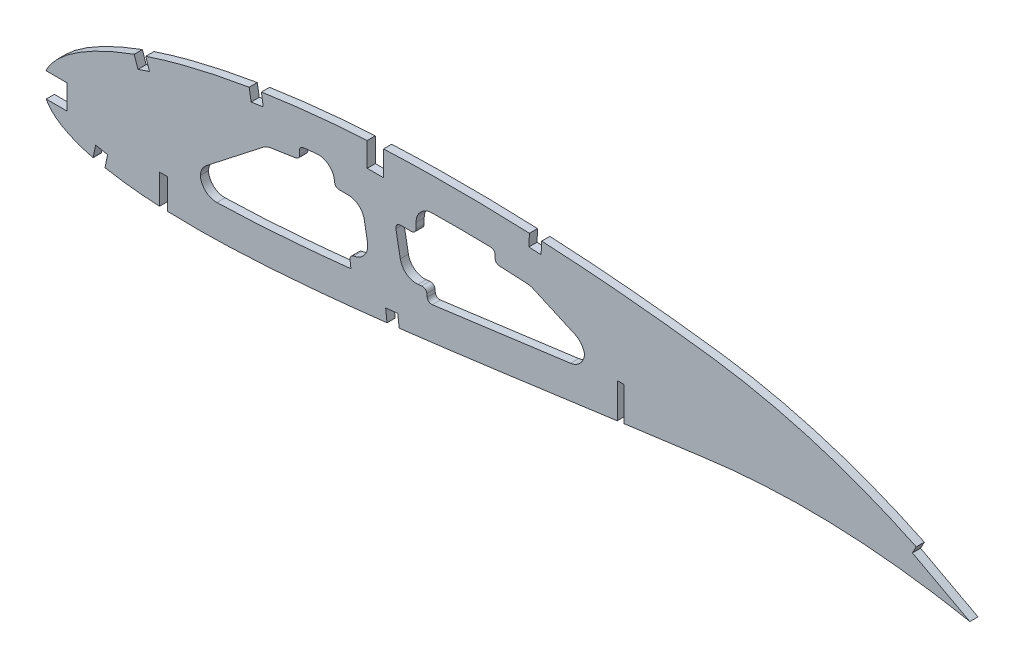
SolidWorks part; units mm, degrees
material "Plywood"
ref_plane "Front Plane" through (0, 0, 0) normal (0, 0, 1) x (1, 0, 0)
ref_plane "Top Plane" through (0, 0, 0) normal (0, 1, 0) x (1, 0, 0)
ref_plane "Right Plane" through (0, 0, 0) normal (1, 0, 0) x (0, 0, -1)
curve "Curve1"
  spline degree 3 poles (383.949, 0.5986, 0) (383.9196, 0.6168, 0) (383.802, 0.6894, 0) (383.5372, 0.8518, 0) (383.0962, 1.1224, 0) (382.4788, 1.4992, 0) (381.6856, 1.9812, 0) (380.716, 2.5651, 0) (379.5708, 3.249, 0) (378.2502, 4.0295, 0) (376.7543, 4.9032, 0) (375.0838, 5.8664, 0) (373.2387, 6.9137, 0) (371.2197, 8.0407, 0) (369.0276, 9.2423, 0) (366.6628, 10.5128, 0) (364.1261, 11.8459, 0) (361.4185, 13.2358, 0) (358.5405, 14.6749, 0) (355.4934, 16.1571, 0) (352.2782, 17.675, 0) (348.8962, 19.2207, 0) (345.3491, 20.7877, 0) (341.638, 22.3663, 0) (337.765, 23.9497, 0) (333.7318, 25.5289, 0) (329.5407, 27.0966, 0) (325.1933, 28.6428, 0) (320.6929, 30.1607, 0) (316.0417, 31.6403, 0) (311.2431, 33.0737, 0) (306.2997, 34.4516, 0) (301.2157, 35.767, 0) (295.9944, 37.0101, 0) (290.6401, 38.1728, 0) (285.1572, 39.2479, 0) (279.5502, 40.2249, 0) (273.8346, 41.1028, 0) (268.1025, 41.8331, 0) (262.3821, 42.5494, 0) (256.6703, 43.2222, 0) (250.8886, 43.8666, 0) (245.0428, 44.4788, 0) (239.1384, 45.057, 0) (233.1816, 45.5987, 0) (227.1785, 46.1022, 0) (221.135, 46.5647, 0) (215.0573, 46.9856, 0) (208.9515, 47.361, 0) (202.8242, 47.6908, 0) (196.6815, 47.9725, 0) (190.5298, 48.2044, 0) (184.3757, 48.385, 0) (178.2255, 48.5125, 0) (172.0859, 48.5861, 0) (165.9633, 48.6039, 0) (159.8643, 48.5655, 0) (153.7954, 48.4696, 0) (147.7632, 48.3149, 0) (141.7741, 48.1011, 0) (135.8345, 47.8283, 0) (129.951, 47.4942, 0) (124.1299, 47.1009, 0) (118.3778, 46.6469, 0) (112.701, 46.1319, 0) (107.1053, 45.5581, 0) (101.5971, 44.9239, 0) (96.1822, 44.2312, 0) (90.8666, 43.4813, 0) (85.6562, 42.6738, 0) (80.5566, 41.8111, 0) (75.5733, 40.894, 0) (70.7116, 39.9252, 0) (65.9768, 38.9049, 0) (61.3739, 37.8363, 0) (56.9076, 36.7211, 0) (52.5828, 35.5615, 0) (48.4038, 34.3602, 0) (44.375, 33.1199, 0) (40.5009, 31.842, 0) (36.7845, 30.5314, 0) (33.2304, 29.1889, 0) (29.8413, 27.8188, 0) (26.6212, 26.4228, 0) (23.5724, 25.0052, 0) (20.6984, 23.5677, 0) (18.0014, 22.1143, 0) (15.4839, 20.6472, 0) (13.1483, 19.1691, 0) (10.9958, 17.6837, 0) (9.0293, 16.1921, 0) (7.2493, 14.698, 0) (5.6571, 13.2036, 0) (4.255, 11.71, 0) (3.0428, 10.2198, 0) (2.0222, 8.7343, 0) (1.1933, 7.2547, 0) (0.558, 5.7822, 0) (0.1157, 4.3176, 0) (-0.1263, 2.863, 0) (-0.1866, 1.4174, 0) (-0.0621, 0.4718, 0) (0, 0, 0) knots 0 0 0 0 0.000254 0.001015 0.002283 0.004057 0.006331 0.009105 0.012374 0.016134 0.02038 0.025106 0.030306 0.035972 0.0421 0.048678 0.055702 0.06316 0.071046 0.07935 0.088063 0.097176 0.106678 0.116562 0.126814 0.137428 0.148394 0.1597 0.171338 0.183298 0.19557 0.208144 0.221012 0.234162 0.247587 0.261277 0.275223 0.289414 0.303771 0.317689 0.331784 0.34604 0.360444 0.374983 0.38964 0.404403 0.419257 0.434187 0.449177 0.464215 0.479284 0.49437 0.509458 0.524532 0.539579 0.554583 0.56953 0.584403 0.599191 0.613877 0.628447 0.642889 0.657186 0.671326 0.685294 0.699078 0.712665 0.726043 0.739198 0.752118 0.764792 0.777208 0.789356 0.801224 0.812804 0.824083 0.835055 0.84571 0.856038 0.866034 0.875689 0.884998 0.893953 0.902553 0.910789 0.918661 0.926166 0.933303 0.940071 0.946475 0.952518 0.958205 0.963547 0.968557 0.97325 0.977651 0.981787 0.985694 0.989415 0.993001 0.996508 1 1 1 1
curve "Curve2"
  spline degree 3 poles (0, 0, 0) (0.0986, -0.4654, 0) (0.2962, -1.3985, 0) (0.8332, -2.7416, 0) (1.5434, -4.0328, 0) (2.4415, -5.2686, 0) (3.5218, -6.4485, 0) (4.7818, -7.574, 0) (6.2202, -8.6443, 0) (7.8352, -9.659, 0) (9.6244, -10.6191, 0) (11.5859, -11.5241, 0) (13.7178, -12.3737, 0) (16.0178, -13.1667, 0) (18.4831, -13.9043, 0) (21.1113, -14.5848, 0) (23.8995, -15.2091, 0) (26.845, -15.7756, 0) (29.9446, -16.2848, 0) (33.195, -16.7366, 0) (36.593, -17.1311, 0) (40.1351, -17.4676, 0) (43.8179, -17.7467, 0) (47.6377, -17.9687, 0) (51.5909, -18.1343, 0) (55.6735, -18.2428, 0) (59.8817, -18.2959, 0) (64.2115, -18.2945, 0) (68.6589, -18.238, 0) (73.2199, -18.1297, 0) (77.8902, -17.9689, 0) (82.6657, -17.7575, 0) (87.5419, -17.4976, 0) (92.5144, -17.1902, 0) (97.5791, -16.8365, 0) (102.7313, -16.4394, 0) (107.9665, -16, 0) (113.2801, -15.5207, 0) (118.6674, -15.0039, 0) (124.1237, -14.4514, 0) (129.6442, -13.8657, 0) (135.2241, -13.2487, 0) (140.8584, -12.6036, 0) (146.5422, -11.9317, 0) (152.2705, -11.2369, 0) (158.0381, -10.5203, 0) (163.84, -9.7848, 0) (169.6711, -9.0339, 0) (175.5259, -8.2674, 0) (181.3995, -7.4908, 0) (187.2862, -6.7036, 0) (193.1809, -5.9096, 0) (199.0781, -5.1115, 0) (204.9721, -4.3094, 0) (210.8578, -3.5066, 0) (216.7295, -2.7054, 0) (222.5817, -1.9059, 0) (228.409, -1.112, 0) (234.2055, -0.3236, 0) (239.9659, 0.4577, 0) (245.6847, 1.2295, 0) (251.3565, 1.9909, 0) (256.9754, 2.7413, 0) (262.5357, 3.4812, 0) (267.9487, 4.188, 0) (273.2002, 4.8993, 0) (278.3079, 5.4825, 0) (283.3519, 5.9802, 0) (288.3377, 6.3883, 0) (293.259, 6.7125, 0) (298.1104, 6.9553, 0) (302.886, 7.1201, 0) (307.5799, 7.2116, 0) (312.186, 7.2323, 0) (316.6983, 7.1886, 0) (321.1107, 7.0842, 0) (325.4171, 6.9238, 0) (329.6115, 6.7126, 0) (333.688, 6.4566, 0) (337.6405, 6.1594, 0) (341.4634, 5.828, 0) (345.1508, 5.4673, 0) (348.6971, 5.0813, 0) (352.0971, 4.6782, 0) (355.3453, 4.2606, 0) (358.4369, 3.8354, 0) (361.3669, 3.4069, 0) (364.1307, 2.9806, 0) (366.7239, 2.5605, 0) (369.1422, 2.1521, 0) (371.3821, 1.7594, 0) (373.4394, 1.3862, 0) (375.3115, 1.0371, 0) (376.9946, 0.7139, 0) (378.4864, 0.4219, 0) (379.7842, 0.1625, 0) (380.886, -0.0608, 0) (381.79, -0.247, 0) (382.4947, -0.3932, 0) (382.9989, -0.4995, 0) (383.3019, -0.5627, 0) (383.4365, -0.5914, 0) (383.4701, -0.5986, 0) knots 0 0 0 0 0.003638 0.007293 0.011028 0.014901 0.018963 0.023258 0.027821 0.032679 0.037853 0.043362 0.049215 0.055422 0.061989 0.068918 0.076211 0.083868 0.091887 0.100266 0.109 0.118085 0.127515 0.137285 0.147388 0.157816 0.168563 0.179619 0.190977 0.202627 0.21456 0.226767 0.239236 0.251959 0.264924 0.27812 0.291536 0.30516 0.318981 0.332985 0.347163 0.361499 0.375981 0.390597 0.405333 0.420175 0.43511 0.450124 0.465203 0.480333 0.495501 0.51069 0.525887 0.541078 0.556247 0.571382 0.586466 0.601485 0.616424 0.631269 0.646007 0.660621 0.675098 0.689423 0.703582 0.716908 0.730009 0.742952 0.755726 0.76832 0.780724 0.792927 0.804916 0.816679 0.828204 0.839475 0.850481 0.861208 0.871639 0.881763 0.891564 0.901027 0.910139 0.918884 0.927249 0.935221 0.942785 0.949928 0.956638 0.962904 0.968712 0.974054 0.978918 0.983297 0.98718 0.990561 0.993433 0.995791 0.99763 0.998946 0.999737 1 1 1 1
sketch "Sketch1" plane through (0, 0, 0) normal (0, 0, 1) x (1, 0, 0)
  line L23 (366.7792, -0.5725) -> (370.31, -1.3257)
  line L24 (367.2372, 0.5725) -> (370.31, -1.3257)
  spline S4 degree 3 poles (0, 0) (0.0943, -0.4452) (0.2833, -1.3376) (0.797, -2.6223) (1.4762, -3.8573) (2.3353, -5.0392) (3.3685, -6.1679) (4.5736, -7.2443) (5.9495, -8.2681) (7.4942, -9.2386) (9.2055, -10.1569) (11.0816, -11.0225) (13.1207, -11.8351) (15.3206, -12.5936) (17.6786, -13.2991) (20.1924, -13.95) (22.8593, -14.5471) (25.6766, -15.0889) (28.6412, -15.576) (31.7502, -16.0081) (35.0002, -16.3855) (38.3882, -16.7073) (41.9107, -16.9743) (45.5643, -17.1866) (49.3453, -17.345) (53.2503, -17.4488) (57.2753, -17.4996) (61.4167, -17.4982) (65.6704, -17.4442) (70.0329, -17.3406) (74.5, -17.1868) (79.0676, -16.9846) (83.7315, -16.736) (88.4877, -16.442) (93.3319, -16.1037) (98.2599, -15.7239) (103.2672, -15.3035) (108.3495, -14.8451) (113.5023, -14.3509) (118.7211, -13.8224) (124.0014, -13.2622) (129.3383, -12.672) (134.7274, -12.055) (140.1638, -11.4124) (145.6428, -10.7478) (151.1593, -10.0624) (156.7087, -9.3589) (162.286, -8.6407) (167.886, -7.9075) (173.5039, -7.1648) (179.1344, -6.4118) (184.7725, -5.6524) (190.4131, -4.889) (196.0505, -4.1218) (201.68, -3.354) (207.2962, -2.5877) (212.8937, -1.823) (218.4673, -1.0636) (224.0115, -0.3095) (229.5212, 0.4377) (234.9911, 1.176) (240.416, 1.9042) (245.7903, 2.622) (251.1086, 3.3297) (256.286, 4.0057) (261.3089, 4.6861) (266.1943, 5.2438) (271.0188, 5.7199) (275.7875, 6.1102) (280.4947, 6.4204) (285.1349, 6.6526) (289.7027, 6.8102) (294.1922, 6.8977) (298.5979, 6.9175) (302.9137, 6.8757) (307.134, 6.7759) (311.253, 6.6224) (315.2649, 6.4204) (319.164, 6.1755) (322.9444, 5.8913) (326.6009, 5.5743) (330.1278, 5.2293) (333.5197, 4.8601) (336.7717, 4.4746) (339.8786, 4.0752) (342.8356, 3.6685) (345.6381, 3.2586) (348.2816, 2.8509) (350.7619, 2.449) (353.075, 2.0585) (355.2173, 1.6829) (357.1852, 1.3259) (358.9757, 0.992) (360.5855, 0.6828) (362.0124, 0.4036) (363.2537, 0.1554) (364.3076, -0.0582) (365.1722, -0.2363) (365.8463, -0.3761) (366.3285, -0.4777) (366.6183, -0.5382) (366.7471, -0.5657) (366.7792, -0.5725) knots 0 0 0 0 0.003638 0.007293 0.011028 0.014901 0.018963 0.023258 0.027821 0.032679 0.037853 0.043362 0.049215 0.055422 0.061989 0.068918 0.076211 0.083868 0.091887 0.100266 0.109 0.118085 0.127515 0.137285 0.147388 0.157816 0.168563 0.179619 0.190977 0.202627 0.21456 0.226767 0.239236 0.251959 0.264924 0.27812 0.291536 0.30516 0.318981 0.332985 0.347163 0.361499 0.375981 0.390597 0.405333 0.420175 0.43511 0.450124 0.465203 0.480333 0.495501 0.51069 0.525887 0.541078 0.556247 0.571382 0.586466 0.601485 0.616424 0.631269 0.646007 0.660621 0.675098 0.689423 0.703582 0.716908 0.730009 0.742952 0.755726 0.76832 0.780724 0.792927 0.804916 0.816679 0.828204 0.839475 0.850481 0.861208 0.871639 0.881763 0.891564 0.901027 0.910139 0.918884 0.927249 0.935221 0.942785 0.949928 0.956638 0.962904 0.968712 0.974054 0.978918 0.983297 0.98718 0.990561 0.993433 0.995791 0.99763 0.998946 0.999737 1 1 1 1
  spline S5 degree 3 poles (367.2372, 0.5725) (367.2091, 0.5899) (367.0967, 0.6594) (366.8434, 0.8147) (366.4216, 1.0735) (365.8311, 1.4339) (365.0724, 1.895) (364.145, 2.4534) (363.0497, 3.1075) (361.7865, 3.8541) (360.3558, 4.6898) (358.7579, 5.6111) (356.9931, 6.6127) (355.062, 7.6908) (352.9654, 8.84) (350.7035, 10.0552) (348.2772, 11.3303) (345.6874, 12.6597) (342.9347, 14.0361) (340.0202, 15.4538) (336.945, 16.9057) (333.7102, 18.3841) (330.3175, 19.8829) (326.7679, 21.3928) (323.0635, 22.9073) (319.2058, 24.4177) (315.1971, 25.9172) (311.039, 27.3961) (306.7345, 28.8479) (302.2857, 30.2631) (297.6959, 31.6342) (292.9677, 32.9521) (288.105, 34.2102) (283.111, 35.3992) (277.9897, 36.5112) (272.7455, 37.5396) (267.3825, 38.474) (261.9157, 39.3138) (256.4331, 40.0123) (250.9617, 40.6974) (245.4985, 41.341) (239.9685, 41.9573) (234.3771, 42.5429) (228.7297, 43.0959) (223.0322, 43.6139) (217.2904, 44.0955) (211.5099, 44.5379) (205.6967, 44.9405) (199.8567, 45.2996) (193.9961, 45.615) (188.1207, 45.8845) (182.2368, 46.1063) (176.3505, 46.279) (170.468, 46.4009) (164.5957, 46.4714) (158.7396, 46.4884) (152.9061, 46.4516) (147.1013, 46.3599) (141.3317, 46.212) (135.6032, 46.0075) (129.9222, 45.7465) (124.2948, 45.427) (118.7271, 45.0508) (113.2253, 44.6165) (107.7956, 44.1239) (102.4435, 43.5751) (97.175, 42.9685) (91.9958, 42.306) (86.9116, 41.5888) (81.9279, 40.8164) (77.0503, 39.9912) (72.2839, 39.114) (67.6338, 38.1874) (63.1051, 37.2115) (58.7025, 36.1894) (54.4306, 35.1228) (50.2941, 34.0137) (46.297, 32.8646) (42.4435, 31.6784) (38.7381, 30.4561) (35.1834, 29.2025) (31.784, 27.9184) (28.5424, 26.6079) (25.4625, 25.2727) (22.5464, 23.9168) (19.7975, 22.5419) (17.2178, 21.1517) (14.8099, 19.7485) (12.5761, 18.3347) (10.5172, 16.914) (8.6363, 15.4873) (6.9338, 14.0582) (5.4109, 12.6289) (4.0698, 11.2003) (2.9103, 9.775) (1.9341, 8.3541) (1.1413, 6.9389) (0.5337, 5.5305) (0.1107, 4.1296) (-0.1208, 2.7384) (-0.1785, 1.3557) (-0.0594, 0.4512) (0, 0) knots 0 0 0 0 0.000254 0.001015 0.002283 0.004057 0.006331 0.009105 0.012374 0.016134 0.02038 0.025106 0.030306 0.035972 0.0421 0.048678 0.055702 0.06316 0.071046 0.07935 0.088063 0.097176 0.106678 0.116562 0.126814 0.137428 0.148394 0.1597 0.171338 0.183298 0.19557 0.208144 0.221012 0.234162 0.247587 0.261277 0.275223 0.289414 0.303771 0.317689 0.331784 0.34604 0.360444 0.374983 0.38964 0.404403 0.419257 0.434187 0.449177 0.464215 0.479284 0.49437 0.509458 0.524532 0.539579 0.554583 0.56953 0.584403 0.599191 0.613877 0.628447 0.642889 0.657186 0.671326 0.685294 0.699078 0.712665 0.726043 0.739198 0.752118 0.764792 0.777208 0.789356 0.801224 0.812804 0.824083 0.835055 0.84571 0.856038 0.866034 0.875689 0.884998 0.893953 0.902553 0.910789 0.918661 0.926166 0.933303 0.940071 0.946475 0.952518 0.958205 0.963547 0.968557 0.97325 0.977651 0.981787 0.985694 0.989415 0.993001 0.996508 1 1 1 1
extrude "Boss-Extrude1" add sketch "Sketch1" along normal blind 3.175
sketch "Sketch2" plane through (0, 0, 0) normal (0, 0, -1) x (-1, 0, 0)
  line L0 (-226.1759, 13.2245) -> (-223.6359, 13.2245)
  line L1 (-226.1759, 0.0342) -> (-226.1759, -1.6012)
  line L2 (-48.3759, -5.601) -> (-48.3759, -17.018)
  line L4 (-226.1759, -1.6012) -> (-223.6359, -0.7835)
  line L5 (-223.6359, -0.7835) -> (-223.6359, 0.0342)
  line L7 (-132.5134, 45.7369) -> (-132.5134, 36.144)
  line L8 (-132.5134, 36.144) -> (-126.1634, 36.144)
  line L9 (-132.5134, 45.7369) -> (-132.5134, 48.5008)
  line L10 (-226.1759, 13.2245) -> (-226.1759, 0.0342)
  line L12 (-132.5134, 48.5008) -> (-126.1634, 46.56)
  line L13 (-126.1634, 46.56) -> (-126.1634, 45.7369)
  line L14 (-45.2009, -5.601) -> (-45.2009, -17.018)
  line L16 (-48.3759, -5.601) -> (-45.2009, -5.601)
  line L17 (-48.3759, -17.018) -> (-48.3759, -19.7506)
  line L19 (-126.1634, 45.7369) -> (-126.1634, 36.144)
  line L20 (-48.3759, -19.7506) -> (-45.2009, -18.0441)
  line L21 (-45.2009, -18.0441) -> (-45.2009, -17.018)
  line L22 (-223.6359, 13.2245) -> (-223.6359, 0.0342)
extrude "Cut-Extrude1" cut sketch "Sketch2" against normal blind 7.62
sketch "Sketch3" plane through (0, 0, 3.175) normal (0, 0, 1) x (1, 0, 0)
  line L1 (-0.4139, 6.4879) -> (9.1111, 6.4879)
  line L2 (133.8957, -12.1377) -> (134.1695, -14.4701)
  line L3 (9.1111, -3.0371) -> (9.1111, 6.4879)
  line L4 (138.6396, -11.5807) -> (138.9134, -13.9131)
  line L5 (24.9672, -9.877) -> (20.307, -8.9078)
  line L6 (134.1695, -14.4701) -> (138.9134, -13.9131)
  line L7 (23.9692, -14.6694) -> (24.9672, -9.877)
  line L9 (41.3214, 26.3939) -> (39.8106, 30.9067)
  line L11 (85.6243, 36.6261) -> (84.9023, 41.3353)
  line L13 (138.0771, -6.8447) -> (133.3478, -7.4064)
  line L15 (138.6396, -11.5807) -> (138.0771, -6.8447)
  line L17 (193.9411, 40.8593) -> (194.1833, 45.6146)
  line L19 (-0.4139, -3.0371) -> (-0.4139, 6.4879)
  line L21 (-0.4139, -3.0371) -> (9.1111, -3.0371)
  line L23 (20.307, -8.9078) -> (19.3375, -13.5718)
  line L25 (80.1398, 40.5723) -> (80.9168, 35.9044)
  line L27 (80.9168, 35.9044) -> (85.6243, 36.6261)
  line L29 (133.3478, -7.4064) -> (133.8957, -12.1377)
  line L31 (189.3949, 45.8428) -> (189.1847, 41.0997)
  line L33 (189.1847, 41.0997) -> (193.9411, 40.8593)
  line L35 (35.312, 29.3422) -> (36.8054, 24.882)
  line L37 (36.8054, 24.882) -> (41.3214, 26.3939)
  line L39 (19.3375, -13.5718) -> (19.0177, -14.9208)
  line L40 (23.9692, -14.6694) -> (23.6495, -16.0185)
  line L41 (19.0177, -14.9208) -> (23.6495, -16.0185)
  arc A1 (194.1833, 45.6146) -> (189.3949, 45.8428) centre (155.1187, -723.9718) ccw
  spline S1 degree 3 poles (39.8106, 30.9067) (39.3989, 30.7692) (37.8946, 30.2613) (36.3966, 29.7352) (35.312, 29.3422) knots 0 0 0 0 0.273428 1 1 1 1
  spline S3 degree 3 poles (84.9023, 41.3353) (83.9797, 41.1935) (82.3915, 40.9435) (80.8049, 40.6833) (80.1398, 40.5723) knots 0 0 0 0 0.580571 1 1 1 1
extrude "Cut-Extrude2" cut sketch "Sketch3" against normal blind 7.62
sketch "Sketch4" plane through (0, 0, 3.175) normal (0, 0, 1) x (1, 0, 0)
  line L0 (124.0505, 23.444) -> (119.8134, 23.444)
  line L1 (61.0759, 3.8422) -> (61.0759, -4.7919)
  line L2 (119.8135, -0.9342) -> (119.2755, 3.7114)
  line L3 (119.2755, 3.7114) -> (127.5024, 4.6885)
  line L4 (140.1395, 6.1895) -> (149.1905, 7.2645)
  line L5 (210.9359, 18.8713) -> (189.752, 28.3548)
  line L6 (113.4634, 23.444) -> (113.4634, 31.88)
  line L7 (99.4216, 30.4365) -> (100.1022, 25.9974)
  line L8 (100.1022, 25.9974) -> (86.8727, 23.9691)
  line L9 (61.0759, 3.8422) -> (86.8727, 23.9691)
  line L10 (210.9359, 25.8286) -> (210.9359, 25.9245)
  line L12 (189.752, 28.3548) -> (175.9385, 29.0531)
  line L13 (124.0505, 23.444) -> (113.4634, 23.444)
  line L15 (127.5024, 4.6885) -> (124.0505, 23.444)
  line L16 (175.9385, 29.0531) -> (176.1387, 33.5719)
  line L17 (145.2134, 33.6045) -> (145.2134, 23.444)
  line L18 (145.2134, 23.444) -> (136.9638, 23.444)
  line L19 (125.5627, 4.4581) -> (127.5024, 4.6885)
  line L20 (149.1905, 7.2645) -> (149.749, 2.5622)
  line L21 (210.9359, 10.7271) -> (210.9359, 18.8713)
  line L23 (140.1395, 6.1895) -> (136.9638, 23.444)
  line L33 (46.7884, 0.749) -> (84.2728, 29.9947) construction
  line L34 (224.9059, 19.5745) -> (191.2608, 34.6367) construction
  line L35 (134.9727, -0.8188) -> (129.3384, 29.794) construction
  line L90 (15.4611, 12.6036) -> (15.4611, -1.4142) construction
  line L91 (15.4611, -1.4142) -> (32.4788, -4.9532) construction
  line L92 (32.4788, -4.9532) -> (31.5192, -9.5611) construction
  line L93 (38.8509, -10.3626) -> (38.8509, 0.749) construction
  line L94 (38.8509, 0.749) -> (54.7259, 0.749) construction
  line L95 (54.7259, 0.749) -> (54.7259, -11.1139) construction
  line L96 (126.857, -6.5565) -> (126.3117, -1.8475) construction
  line L97 (126.3117, -1.8475) -> (143.6338, 0.2099) construction
  line L98 (143.6338, 0.2099) -> (144.1962, -4.5249) construction
  line L99 (217.2859, 5.1839) -> (217.2859, 19.5745) construction
  line L100 (217.2859, 19.5745) -> (232.5259, 19.5745) construction
  line L101 (232.5259, 19.5745) -> (232.5259, 7.2506) construction
  line L102 (200.2001, 38.9114) -> (199.9599, 34.1969) construction
  line L103 (199.9599, 34.1969) -> (182.5616, 35.0764) construction
  line L104 (182.5616, 35.0764) -> (182.7677, 39.7263) construction
  line L105 (138.8634, 39.7674) -> (138.8634, 29.794) construction
  line L106 (138.8634, 29.794) -> (119.8134, 29.794) construction
  line L107 (119.8134, 29.794) -> (119.8134, 38.7525) construction
  line L108 (92.1584, 35.9089) -> (92.8632, 31.3117) construction
  line L109 (92.8632, 31.3117) -> (75.6823, 28.6777) construction
  line L110 (75.6823, 28.6777) -> (74.9393, 33.1419) construction
  line L111 (47.9131, 26.7069) -> (49.3588, 22.3884) construction
  line L112 (49.3588, 22.3884) -> (32.7999, 16.8445) construction
  line L113 (32.7999, 16.8445) -> (31.4358, 20.9189) construction
  spline S1 degree 3 poles (61.0759, -4.7919) (65.956, -4.7644) (75.6976, -4.4951) (90.3945, -3.6335) (105.0964, -2.4282) (114.9126, -1.4532) (119.8135, -0.9342) knots 0.088297 0.088297 0.088297 0.088297 0.294057 0.499818 0.705579 0.911339 0.911339 0.911339 0.911339
  spline S3 degree 3 poles (113.4634, 31.88) (112.2906, 31.7785) (109.9455, 31.5663) (106.4329, 31.2203) (102.9244, 30.8456) (100.5889, 30.5762) (99.4216, 30.4365) knots 0.248835 0.248835 0.248835 0.248835 0.377634 0.506434 0.635234 0.764034 0.764034 0.764034 0.764034
  spline S5 degree 3 poles (176.1387, 33.5719) (173.5606, 33.6369) (168.4029, 33.7373) (160.6696, 33.7956) (152.938, 33.7586) (147.7883, 33.6675) (145.2134, 33.6045) knots 0.147373 0.147373 0.147373 0.147373 0.325248 0.503123 0.680998 0.858873 0.858873 0.858873 0.858873
  spline S7 degree 3 poles (149.749, 2.5622) (154.8468, 3.2019) (165.0342, 4.5157) (180.3292, 6.5582) (195.6275, 8.6359) (205.8337, 10.0311) (210.9359, 10.7271) knots 0.086693 0.086693 0.086693 0.086693 0.296227 0.505762 0.715296 0.924831 0.924831 0.924831 0.924831
  spline S29 degree 3 poles (31.4358, 20.9189) (28.6531, 19.7653) (25.916, 18.5237) (21.9074, 16.4737) (20.5873, 15.759) (17.9891, 14.2488) (16.7091, 13.4524) (15.4611, 12.6036) knots 0 0 0 0 0.5 0.5 0.75 0.75 1 1 1 1 construction
  spline S30 degree 3 poles (31.5192, -9.5611) (33.9561, -9.8911) (36.4008, -10.1525) (38.8509, -10.3626) knots 0 0 0 0 1 1 1 1 construction
  spline S31 degree 3 poles (54.7259, -11.1139) (60.7538, -11.2031) (66.7785, -11.1065) (78.8236, -10.6715) (84.8424, -10.3327) (96.8659, -9.4865) (102.8724, -8.9793) (114.8725, -7.8476) (120.8667, -7.2227) (126.857, -6.5565) knots 0 0 0 0 0.25 0.25 0.5 0.5 0.75 0.75 1 1 1 1 construction
  spline S32 degree 3 poles (144.1962, -4.5249) (156.3939, -3.0317) (168.5773, -1.4251) (192.9351, 1.8535) (205.1095, 3.5262) (217.2859, 5.1839) knots 0 0 0 0 0.5 0.5 1 1 1 1 construction
  spline S33 degree 3 poles (232.5259, 7.2506) (236.7454, 7.8194) (240.9653, 8.3846) (247.2957, 9.2284) (249.406, 9.5085) (252.572, 9.9246) (253.6273, 10.0631) (255.7377, 10.3424) (256.7926, 10.4843) (258.903, 10.7638) (259.9585, 10.901) (262.0714, 11.1604) (263.1287, 11.2834) (266.3027, 11.6351) (268.4217, 11.8485) (274.7855, 12.4209) (279.0307, 12.7117) (287.5261, 13.1156) (291.7763, 13.2287) (300.2819, 13.2775) (304.5386, 13.2148) (317.3074, 12.7665) (325.7774, 12.1249) (334.2082, 11.1674) knots 0 0 0 0 0.125 0.125 0.1875 0.1875 0.21875 0.21875 0.25 0.25 0.28125 0.28125 0.3125 0.3125 0.375 0.375 0.5 0.5 0.625 0.625 0.75 0.75 1 1 1 1 construction
  spline S34 degree 3 poles (334.2082, 11.1674) (331.593, 12.3814) (328.9576, 13.5555) (323.6447, 15.8208) (320.9638, 16.9136) (312.8924, 20.0522) (307.47, 21.9608) (291.0773, 27.1309) (279.9822, 29.8393) (265.8998, 32.2791) (263.0735, 32.7235) (258.8151, 33.3063) (257.3929, 33.4883) (254.5475, 33.8483) (253.1245, 34.0271) (246.0062, 34.9053) (240.2966, 35.5479) (223.1381, 37.304) (211.6798, 38.2388) (200.2001, 38.9114) knots 0 0 0 0 0.0625 0.0625 0.125 0.125 0.25 0.25 0.5 0.5 0.5625 0.5625 0.59375 0.59375 0.625 0.625 0.75 0.75 1 1 1 1 construction
  spline S35 degree 3 poles (182.7677, 39.7263) (175.4529, 39.9792) (168.1344, 40.1179) (153.497, 40.1411) (146.178, 40.0263) (138.8634, 39.7674) knots 0 0 0 0 0.5 0.5 1 1 1 1 construction
  spline S36 degree 3 poles (119.8134, 38.7525) (110.5679, 38.0873) (101.3431, 37.1604) (92.1584, 35.9089) knots 0 0 0 0 1 1 1 1 construction
  spline S37 degree 3 poles (74.9393, 33.1419) (70.3845, 32.2908) (65.8479, 31.3424) (56.8317, 29.213) (52.3534, 28.033) (47.9131, 26.7069) knots 0 0 0 0 0.5 0.5 1 1 1 1 construction
extrude "Cut-Extrude3" cut sketch "Sketch4" against normal blind 7.62 contours L6 S3 L7 L8 L9 L1 S1 L2 L3 L15 L0 L13 | L20 S7 L21 L5 L12 L16 S5 L17 L18 L23 L4
fillet "Fillet1" radius 6.35 11 edges at (210.9359, 10.7271, 1.5875) (210.9359, 18.8713, 1.5875) (189.752, 28.3548, 1.5875) (140.1395, 6.1895, 1.5875) (145.2134, 33.6045, 1.5875) (113.4634, 31.88, 1.5875) (124.0505, 23.444, 1.5875) (127.5024, 4.6885, 1.5875) (86.8727, 23.9691, 1.5875) (61.0759, 3.8422, 1.5875) (61.0759, -4.7919, 1.5875)
fillet "Fillet2" radius 1.778 10 edges at (175.9385, 29.0531, 1.5875) (176.1387, 33.5719, 1.5875) (145.2134, 23.444, 1.5875) (136.9638, 23.444, 1.5875) (149.749, 2.5622, 1.5875) (149.1905, 7.2645, 1.5875) (119.2755, 3.7114, 1.5875) (113.4634, 23.444, 1.5875) (99.4216, 30.4365, 1.5875) (100.1022, 25.9974, 1.5875)
sketch "Sketch5" plane through (0, 0, 3.175) normal (0, 0, 1) x (1, 0, 0)
  line L0 (340.1843, 15.368) -> (338.6864, 12.5685)
  line L1 (340.1843, 15.368) -> (362.5799, 3.3848)
  line L2 (338.6864, 12.5685) -> (361.082, 0.5854)
  line L3 (362.5799, 3.3848) -> (361.082, 0.5854)
  line L33 (0.9572, 6.4879) -> (9.1111, 6.4879)
  line L34 (9.1111, 6.4879) -> (9.1111, -3.0371)
  line L35 (9.1111, -3.0371) -> (1.0356, -3.0371)
  line L36 (19.3035, -13.715) -> (19.3375, -13.5718)
  line L37 (19.3375, -13.5718) -> (20.307, -8.9078)
  line L38 (20.307, -8.9078) -> (24.9672, -9.877)
  line L39 (24.9672, -9.877) -> (23.9692, -14.6694)
  line L40 (23.9692, -14.6694) -> (23.9494, -14.7527)
  line L41 (45.2009, -17.1581) -> (45.2009, -5.601)
  line L42 (45.2009, -5.601) -> (48.3759, -5.601)
  line L43 (48.3759, -5.601) -> (48.3759, -17.3002)
  line L44 (133.8969, -12.1481) -> (133.8957, -12.1377)
  line L45 (133.8957, -12.1377) -> (133.3478, -7.4064)
  line L46 (133.3478, -7.4064) -> (138.0771, -6.8447)
  line L47 (138.0771, -6.8447) -> (138.6396, -11.5807)
  line L48 (138.6396, -11.5807) -> (138.6408, -11.5913)
  line L49 (223.6359, -0.3609) -> (223.6359, 13.2245)
  line L50 (223.6359, 13.2245) -> (226.1759, 13.2245)
  line L51 (226.1759, 13.2245) -> (226.1759, -0.0161)
  line L52 (366.7792, -0.5725) -> (370.31, -1.3257)
  line L53 (370.31, -1.3257) -> (367.2372, 0.5725)
  line L54 (194.1825, 45.5979) -> (193.9411, 40.8593)
  line L55 (193.9411, 40.8593) -> (189.1847, 41.0997)
  line L56 (189.1847, 41.0997) -> (189.394, 45.8221)
  line L57 (132.5134, 45.863) -> (132.5134, 36.144)
  line L58 (132.5134, 36.144) -> (126.1634, 36.144)
  line L59 (126.1634, 36.144) -> (126.1634, 45.5297)
  line L60 (84.9115, 41.2755) -> (85.6243, 36.6261)
  line L61 (85.6243, 36.6261) -> (80.9168, 35.9044)
  line L62 (80.9168, 35.9044) -> (80.1498, 40.512)
  line L63 (39.8414, 30.8149) -> (41.3214, 26.3939)
  line L64 (41.3214, 26.3939) -> (36.8054, 24.882)
  line L65 (36.8054, 24.882) -> (35.3441, 29.2465)
  line L66 (0.9572, 6.4879) -> (9.1111, 6.4879)
  line L67 (9.1111, 6.4879) -> (9.1111, -3.0371)
  line L68 (9.1111, -3.0371) -> (1.0356, -3.0371)
  line L69 (19.3035, -13.715) -> (19.3375, -13.5718)
  line L70 (19.3375, -13.5718) -> (20.307, -8.9078)
  line L71 (20.307, -8.9078) -> (24.9672, -9.877)
  line L72 (24.9672, -9.877) -> (23.9692, -14.6694)
  line L73 (23.9692, -14.6694) -> (23.9494, -14.7527)
  line L74 (45.2009, -17.1581) -> (45.2009, -5.601)
  line L75 (45.2009, -5.601) -> (48.3759, -5.601)
  line L76 (48.3759, -5.601) -> (48.3759, -17.3002)
  line L77 (133.8969, -12.1481) -> (133.8957, -12.1377)
  line L78 (133.8957, -12.1377) -> (133.3478, -7.4064)
  line L79 (133.3478, -7.4064) -> (138.0771, -6.8447)
  line L80 (138.0771, -6.8447) -> (138.6396, -11.5807)
  line L81 (138.6396, -11.5807) -> (138.6408, -11.5913)
  line L82 (223.6359, -0.3609) -> (223.6359, 13.2245)
  line L83 (223.6359, 13.2245) -> (226.1759, 13.2245)
  line L84 (226.1759, 13.2245) -> (226.1759, -0.0161)
  line L85 (366.7792, -0.5725) -> (370.31, -1.3257)
  line L86 (370.31, -1.3257) -> (367.2372, 0.5725)
  line L87 (194.1825, 45.5979) -> (193.9411, 40.8593)
  line L88 (193.9411, 40.8593) -> (189.1847, 41.0997)
  line L89 (189.1847, 41.0997) -> (189.394, 45.8221)
  line L90 (132.5134, 45.863) -> (132.5134, 36.144)
  line L91 (132.5134, 36.144) -> (126.1634, 36.144)
  line L92 (126.1634, 36.144) -> (126.1634, 45.5297)
  line L93 (84.9115, 41.2755) -> (85.6243, 36.6261)
  line L94 (85.6243, 36.6261) -> (80.9168, 35.9044)
  line L95 (80.9168, 35.9044) -> (80.1498, 40.512)
  line L96 (39.8414, 30.8149) -> (41.3214, 26.3939)
  line L97 (41.3214, 26.3939) -> (36.8054, 24.882)
  line L98 (36.8054, 24.882) -> (35.3441, 29.2465)
  spline S10 degree 3 poles (-1602.2186, 3650.0051) (487.3789, -131.6192) (206.9819, 94.095) (31.784, 27.9184) (28.5424, 26.6079) (25.4625, 25.2727) (22.5464, 23.9168) (19.7975, 22.5419) (17.2178, 21.1517) (14.8099, 19.7485) (12.5761, 18.3347) (10.5172, 16.914) (8.6363, 15.4873) (6.9338, 14.0582) (5.4109, 12.6289) (4.0698, 11.2003) (2.9103, 9.775) (1.9341, 8.3541) (-20.7317, -32.1056) (141.9822, -164.1766) (3983.6471, 308.8367) knots -0.544959 -0.544959 -0.544959 -0.544959 0.875689 0.884998 0.893953 0.902553 0.910789 0.918661 0.926166 0.933303 0.940071 0.946475 0.952518 0.958205 0.963547 0.968557 0.97325 0.977651 0.981787 1.329029 1.329029 1.329029 1.329029 only from (35.3441, 29.2465) to (0.9572, 6.4879)
  spline S11 degree 3 poles (2949.6013, -2676.1015) (249.915, 275.4573) (-28.9452, 37.9974) (2.3353, -5.0392) (3.3685, -6.1679) (4.5736, -7.2443) (5.9495, -8.2681) (7.4942, -9.2386) (9.2055, -10.1569) (11.0816, -11.0225) (13.1207, -11.8351) (15.3206, -12.5936) (116.8044, -42.9584) (283.113, 163.1405) (-1566.1338, -3678.5939) knots -0.405957 -0.405957 -0.405957 -0.405957 0.011028 0.014901 0.018963 0.023258 0.027821 0.032679 0.037853 0.043362 0.049215 0.055422 0.061989 0.897212 0.897212 0.897212 0.897212 only from (1.0356, -3.0371) to (19.3035, -13.715)
  spline S12 degree 3 poles (1065.9481, 3834.2944) (-164.825, 196.4215) (-84.1296, 2.9522) (28.6412, -15.576) (31.7502, -16.0081) (35.0002, -16.3855) (38.3882, -16.7073) (232.9912, -31.4577) (444.7882, 229.5505) (-286.8072, -3972.5643) knots -0.814737 -0.814737 -0.814737 -0.814737 0.083868 0.091887 0.100266 0.109 0.118085 0.127515 1.671641 1.671641 1.671641 1.671641 only from (23.9494, -14.7527) to (45.2009, -17.1581)
  spline S13 degree 3 poles (199.4193, 3945.0482) (-332.1325, 221.8434) (-143.9877, -12.2071) (53.2503, -17.4488) (57.2753, -17.4996) (61.4167, -17.4982) (65.6704, -17.4442) (70.0329, -17.3406) (74.5, -17.1868) (79.0676, -16.9846) (83.7315, -16.736) (88.4877, -16.442) (93.3319, -16.1037) (98.2599, -15.7239) (103.2672, -15.3035) (108.3495, -14.8451) (113.5023, -14.3509) (118.7211, -13.8224) (124.0014, -13.2622) (638.367, 43.6175) (1119.1061, 383.178) (1771.0517, -3371.2138) knots -1.411295 -1.411295 -1.411295 -1.411295 0.147388 0.157816 0.168563 0.179619 0.190977 0.202627 0.21456 0.226767 0.239236 0.251959 0.264924 0.27812 0.291536 0.30516 0.318981 0.332985 0.347163 0.361499 4.476796 4.476796 4.476796 4.476796 only from (48.3759, -17.3002) to (133.8969, -12.1481)
  spline S14 degree 3 poles (-1227.5928, 3651.2454) (-525.6727, 0.0992) (-185.4811, -50.9151) (145.6428, -10.7478) (151.1593, -10.0624) (156.7087, -9.3589) (162.286, -8.6407) (167.886, -7.9075) (173.5039, -7.1648) (179.1344, -6.4118) (184.7725, -5.6524) (190.4131, -4.889) (196.0505, -4.1218) (201.68, -3.354) (207.2962, -2.5877) (212.8937, -1.823) (746.9825, 70.9413) (1281.5459, 126.244) (2270.053, -3174.2029) knots -2.25069 -2.25069 -2.25069 -2.25069 0.390597 0.405333 0.420175 0.43511 0.450124 0.465203 0.480333 0.495501 0.51069 0.525887 0.541078 0.556247 0.571382 0.586466 0.601485 4.887536 4.887536 4.887536 4.887536 only from (138.6408, -11.5913) to (223.6359, -0.3609)
  spline S15 degree 3 poles (-1582.265, 3373.7911) (-655.3394, -155.2415) (-213.4868, -59.3515) (234.9911, 1.176) (240.416, 1.9042) (245.7903, 2.622) (251.1086, 3.3297) (256.286, 4.0057) (261.3089, 4.6861) (266.1943, 5.2438) (271.0188, 5.7199) (275.7875, 6.1102) (280.4947, 6.4204) (285.1349, 6.6526) (289.7027, 6.8102) (294.1922, 6.8977) (298.5979, 6.9175) (302.9137, 6.8757) (307.134, 6.7759) (311.253, 6.6224) (315.2649, 6.4204) (319.164, 6.1755) (322.9444, 5.8913) (326.6009, 5.5743) (330.1278, 5.2293) (333.5197, 4.8601) (336.7717, 4.4746) (339.8786, 4.0752) (342.8356, 3.6685) (345.6381, 3.2586) (348.2816, 2.8509) (350.7619, 2.449) (353.075, 2.0585) (355.2173, 1.6829) (357.1852, 1.3259) (358.9757, 0.992) (360.5855, 0.6828) (362.0124, 0.4036) (363.2537, 0.1554) (364.3076, -0.0582) (365.1722, -0.2363) (365.8463, -0.3761) (366.3285, -0.4777) (382.0747, -3.7643) (395.9088, -15.2969) (1239.7432, 3898.2215) knots -2.963065 -2.963065 -2.963065 -2.963065 0.631269 0.646007 0.660621 0.675098 0.689423 0.703582 0.716908 0.730009 0.742952 0.755726 0.76832 0.780724 0.792927 0.804916 0.816679 0.828204 0.839475 0.850481 0.861208 0.871639 0.881763 0.891564 0.901027 0.910139 0.918884 0.927249 0.935221 0.942785 0.949928 0.956638 0.962904 0.968712 0.974054 0.978918 0.983297 0.98718 0.990561 0.993433 0.995791 0.99763 0.998946 0.999737 1.126432 1.126432 1.126432 1.126432 only from (226.1759, -0.0161) to (366.7792, -0.5725)
  spline S16 degree 3 poles (2508.7046, 3375.6327) (393.3418, -24.3481) (382.1546, -8.5769) (366.8434, 0.8147) (366.4216, 1.0735) (365.8311, 1.4339) (365.0724, 1.895) (364.145, 2.4534) (363.0497, 3.1075) (361.7865, 3.8541) (360.3558, 4.6898) (358.7579, 5.6111) (356.9931, 6.6127) (355.062, 7.6908) (352.9654, 8.84) (350.7035, 10.0552) (348.2772, 11.3303) (345.6874, 12.6597) (342.9347, 14.0361) (340.0202, 15.4538) (336.945, 16.9057) (333.7102, 18.3841) (330.3175, 19.8829) (326.7679, 21.3928) (323.0635, 22.9073) (319.2058, 24.4177) (315.1971, 25.9172) (311.039, 27.3961) (306.7345, 28.8479) (302.2857, 30.2631) (297.6959, 31.6342) (292.9677, 32.9521) (288.105, 34.2102) (283.111, 35.3992) (277.9897, 36.5112) (272.7455, 37.5396) (267.3825, 38.474) (261.9157, 39.3138) (256.4331, 40.0123) (250.9617, 40.6974) (245.4985, 41.341) (239.9685, 41.9573) (234.3771, 42.5429) (228.7297, 43.0959) (223.0322, 43.6139) (217.2904, 44.0955) (211.5099, 44.5379) (205.6967, 44.9405) (-228.1779, 71.6192) (-681.203, -267.6083) (-675.5968, -3702.6072) knots -0.135735 -0.135735 -0.135735 -0.135735 0.000254 0.001015 0.002283 0.004057 0.006331 0.009105 0.012374 0.016134 0.02038 0.025106 0.030306 0.035972 0.0421 0.048678 0.055702 0.06316 0.071046 0.07935 0.088063 0.097176 0.106678 0.116562 0.126814 0.137428 0.148394 0.1597 0.171338 0.183298 0.19557 0.208144 0.221012 0.234162 0.247587 0.261277 0.275223 0.289414 0.303771 0.317689 0.331784 0.34604 0.360444 0.374983 0.38964 0.404403 0.419257 0.434187 0.449177 3.759363 3.759363 3.759363 3.759363 only from (367.2372, 0.5725) to (194.1825, 45.5979)
  spline S17 degree 3 poles (460.178, 3715.5012) (1314.498, -697.6329) (763.9908, 24.179) (182.2368, 46.1063) (176.3505, 46.279) (170.468, 46.4009) (164.5957, 46.4714) (158.7396, 46.4884) (152.9061, 46.4516) (147.1013, 46.3599) (141.3317, 46.212) (-178.8579, 34.7818) (-486.0753, -248.4623) (-146.1286, -3859.2369) knots -3.963796 -3.963796 -3.963796 -3.963796 0.479284 0.49437 0.509458 0.524532 0.539579 0.554583 0.56953 0.584403 0.599191 0.613877 3.046229 3.046229 3.046229 3.046229 only from (189.394, 45.8221) to (132.5134, 45.863)
  spline S18 degree 3 poles (-1510.0367, -2975.3791) (1394.7614, -924.1986) (725.0164, 86.011) (118.7271, 45.0508) (113.2253, 44.6165) (107.7956, 44.1239) (102.4435, 43.5751) (97.175, 42.9685) (91.9958, 42.306) (-223.391, -2.1861) (-478.2112, -444.3719) (772.3728, -3802.4408) knots -3.997859 -3.997859 -3.997859 -3.997859 0.642889 0.657186 0.671326 0.685294 0.699078 0.712665 0.726043 0.739198 3.159984 3.159984 3.159984 3.159984 only from (126.1634, 45.5297) to (84.9115, 41.2755)
  spline S19 degree 3 poles (-831.3268, 3851.7114) (793.5888, -301.4835) (393.2623, 98.1868) (72.2839, 39.114) (67.6338, 38.1874) (63.1051, 37.2115) (58.7025, 36.1894) (54.4306, 35.1228) (50.2941, 34.0137) (46.297, 32.8646) (-153.8604, -28.7536) (-253.4913, -401.3633) (1680.0646, -3569.3549) knots -1.718338 -1.718338 -1.718338 -1.718338 0.764792 0.777208 0.789356 0.801224 0.812804 0.824083 0.835055 0.84571 0.856038 2.444169 2.444169 2.444169 2.444169 only from (80.1498, 40.512) to (39.8414, 30.8149)
  spline S20 degree 3 poles (35.3441, 29.2465) (35.278, 29.2225) (34.0737, 28.7833) (31.784, 27.9184) (28.5424, 26.6079) (25.4625, 25.2727) (22.5464, 23.9168) (19.7975, 22.5419) (17.2178, 21.1517) (14.8099, 19.7485) (12.5761, 18.3347) (10.5172, 16.914) (8.6363, 15.4873) (6.9338, 14.0582) (5.4109, 12.6289) (4.0698, 11.2003) (2.9103, 9.775) (1.9341, 8.3541) (1.3159, 7.2504) (1.0201, 6.6263) (0.9572, 6.4879) knots 0.875148 0.875148 0.875148 0.875148 0.875689 0.884998 0.893953 0.902553 0.910789 0.918661 0.926166 0.933303 0.940071 0.946475 0.952518 0.958205 0.963547 0.968557 0.97325 0.977651 0.981787 0.982955 0.982955 0.982955 0.982955
  spline S21 degree 3 poles (1.0356, -3.0371) (1.1772, -3.3064) (1.5719, -3.989) (2.3353, -5.0392) (3.3685, -6.1679) (4.5736, -7.2443) (5.9495, -8.2681) (7.4942, -9.2386) (9.2055, -10.1569) (11.0816, -11.0225) (13.1207, -11.8351) (15.3206, -12.5936) (17.3995, -13.2156) (18.747, -13.5738) (19.3035, -13.715) knots 0.008594 0.008594 0.008594 0.008594 0.011028 0.014901 0.018963 0.023258 0.027821 0.032679 0.037853 0.043362 0.049215 0.055422 0.061989 0.066586 0.066586 0.066586 0.066586
  spline S22 degree 3 poles (23.9494, -14.7527) (24.5102, -14.8625) (26.0564, -15.1513) (28.6412, -15.576) (31.7502, -16.0081) (35.0002, -16.3855) (38.3882, -16.7073) (41.8034, -16.9662) (44.0898, -17.1008) (45.2009, -17.1581) knots 0.079293 0.079293 0.079293 0.079293 0.083868 0.091887 0.100266 0.109 0.118085 0.127515 0.136423 0.136423 0.136423 0.136423
  spline S23 degree 3 poles (48.3759, -17.3002) (48.6856, -17.3119) (50.2968, -17.3703) (53.2503, -17.4488) (57.2753, -17.4996) (61.4167, -17.4982) (65.6704, -17.4442) (70.0329, -17.3406) (74.5, -17.1868) (79.0676, -16.9846) (83.7315, -16.736) (88.4877, -16.442) (93.3319, -16.1037) (98.2599, -15.7239) (103.2672, -15.3035) (108.3495, -14.8451) (113.5023, -14.3509) (118.7211, -13.8224) (124.0014, -13.2622) (129.067, -12.702) (132.3715, -12.3247) (133.8969, -12.1481) knots 0.144906 0.144906 0.144906 0.144906 0.147388 0.157816 0.168563 0.179619 0.190977 0.202627 0.21456 0.226767 0.239236 0.251959 0.264924 0.27812 0.291536 0.30516 0.318981 0.332985 0.347163 0.361499 0.373795 0.373795 0.373795 0.373795
  spline S24 degree 3 poles (138.6408, -11.5913) (139.1435, -11.5315) (141.4734, -11.2535) (145.6428, -10.7478) (151.1593, -10.0624) (156.7087, -9.3589) (162.286, -8.6407) (167.886, -7.9075) (173.5039, -7.1648) (179.1344, -6.4118) (184.7725, -5.6524) (190.4131, -4.889) (196.0505, -4.1218) (201.68, -3.354) (207.2962, -2.5877) (212.8937, -1.823) (218.3382, -1.0812) (221.9162, -0.5945) (223.6359, -0.3609) knots 0.386544 0.386544 0.386544 0.386544 0.390597 0.405333 0.420175 0.43511 0.450124 0.465203 0.480333 0.495501 0.51069 0.525887 0.541078 0.556247 0.571382 0.586466 0.601485 0.615381 0.615381 0.615381 0.615381
  spline S25 degree 3 poles (226.1759, -0.0161) (227.2954, 0.1358) (230.2388, 0.5346) (234.9911, 1.176) (240.416, 1.9042) (245.7903, 2.622) (251.1086, 3.3297) (256.286, 4.0057) (261.3089, 4.6861) (266.1943, 5.2438) (271.0188, 5.7199) (275.7875, 6.1102) (280.4947, 6.4204) (285.1349, 6.6526) (289.7027, 6.8102) (294.1922, 6.8977) (298.5979, 6.9175) (302.9137, 6.8757) (307.134, 6.7759) (311.253, 6.6224) (315.2649, 6.4204) (319.164, 6.1755) (322.9444, 5.8913) (326.6009, 5.5743) (330.1278, 5.2293) (333.5197, 4.8601) (336.7717, 4.4746) (339.8786, 4.0752) (342.8356, 3.6685) (345.6381, 3.2586) (348.2816, 2.8509) (350.7619, 2.449) (353.075, 2.0585) (355.2173, 1.6829) (357.1852, 1.3259) (358.9757, 0.992) (360.5855, 0.6828) (362.0124, 0.4036) (363.2537, 0.1554) (364.3076, -0.0582) (365.1722, -0.2363) (365.8463, -0.3761) (366.3285, -0.4777) (366.6183, -0.5382) (366.7471, -0.5657) (366.7792, -0.5725) knots 0.622223 0.622223 0.622223 0.622223 0.631269 0.646007 0.660621 0.675098 0.689423 0.703582 0.716908 0.730009 0.742952 0.755726 0.76832 0.780724 0.792927 0.804916 0.816679 0.828204 0.839475 0.850481 0.861208 0.871639 0.881763 0.891564 0.901027 0.910139 0.918884 0.927249 0.935221 0.942785 0.949928 0.956638 0.962904 0.968712 0.974054 0.978918 0.983297 0.98718 0.990561 0.993433 0.995791 0.99763 0.998946 0.999737 1 1 1 1
  spline S26 degree 3 poles (367.2372, 0.5725) (367.2091, 0.5899) (367.0967, 0.6594) (366.8434, 0.8147) (366.4216, 1.0735) (365.8311, 1.4339) (365.0724, 1.895) (364.145, 2.4534) (363.0497, 3.1075) (361.7865, 3.8541) (360.3558, 4.6898) (358.7579, 5.6111) (356.9931, 6.6127) (355.062, 7.6908) (352.9654, 8.84) (350.7035, 10.0552) (348.2772, 11.3303) (345.6874, 12.6597) (342.9347, 14.0361) (340.0202, 15.4538) (336.945, 16.9057) (333.7102, 18.3841) (330.3175, 19.8829) (326.7679, 21.3928) (323.0635, 22.9073) (319.2058, 24.4177) (315.1971, 25.9172) (311.039, 27.3961) (306.7345, 28.8479) (302.2857, 30.2631) (297.6959, 31.6342) (292.9677, 32.9521) (288.105, 34.2102) (283.111, 35.3992) (277.9897, 36.5112) (272.7455, 37.5396) (267.3825, 38.474) (261.9157, 39.3138) (256.4331, 40.0123) (250.9617, 40.6974) (245.4985, 41.341) (239.9685, 41.9573) (234.3771, 42.5429) (228.7297, 43.0959) (223.0322, 43.6139) (217.2904, 44.0955) (211.5099, 44.5379) (205.6967, 44.9405) (199.9176, 45.2958) (196.0762, 45.503) (194.1825, 45.5979) knots 0 0 0 0 0.000254 0.001015 0.002283 0.004057 0.006331 0.009105 0.012374 0.016134 0.02038 0.025106 0.030306 0.035972 0.0421 0.048678 0.055702 0.06316 0.071046 0.07935 0.088063 0.097176 0.106678 0.116562 0.126814 0.137428 0.148394 0.1597 0.171338 0.183298 0.19557 0.208144 0.221012 0.234162 0.247587 0.261277 0.275223 0.289414 0.303771 0.317689 0.331784 0.34604 0.360444 0.374983 0.38964 0.404403 0.419257 0.434187 0.449177 0.463746 0.463746 0.463746 0.463746
  spline S27 degree 3 poles (189.394, 45.8221) (188.9702, 45.8406) (186.5849, 45.9424) (182.2368, 46.1063) (176.3505, 46.279) (170.468, 46.4009) (164.5957, 46.4714) (158.7396, 46.4884) (152.9061, 46.4516) (147.1013, 46.3599) (141.3317, 46.212) (136.4729, 46.0385) (133.5383, 45.9106) (132.5134, 45.863) knots 0.476024 0.476024 0.476024 0.476024 0.479284 0.49437 0.509458 0.524532 0.539579 0.554583 0.56953 0.584403 0.599191 0.613877 0.621761 0.621761 0.621761 0.621761
  spline S28 degree 3 poles (126.1634, 45.5297) (125.5344, 45.4929) (123.0482, 45.3428) (118.7271, 45.0508) (113.2253, 44.6165) (107.7956, 44.1239) (102.4435, 43.5751) (97.175, 42.9685) (91.9958, 42.306) (87.9184, 41.7308) (85.5684, 41.3764) (84.9115, 41.2755) knots 0.638048 0.638048 0.638048 0.638048 0.642889 0.657186 0.671326 0.685294 0.699078 0.712665 0.726043 0.739198 0.744304 0.744304 0.744304 0.744304
  spline S29 degree 3 poles (80.1498, 40.512) (79.1055, 40.3374) (76.4694, 39.8843) (72.2839, 39.114) (67.6338, 38.1874) (63.1051, 37.2115) (58.7025, 36.1894) (54.4306, 35.1228) (50.2941, 34.0137) (46.297, 32.8646) (42.8273, 31.7965) (40.6944, 31.1001) (39.8414, 30.8149) knots 0.756656 0.756656 0.756656 0.756656 0.764792 0.777208 0.789356 0.801224 0.812804 0.824083 0.835055 0.84571 0.856038 0.862949 0.862949 0.862949 0.862949
  dimension "D2" = 25.4
  dimension "D3" = 3.175
  dimension "D1" = 0
extrude "Cut-Extrude4" cut sketch "Sketch5" against normal through all contours L3 L1 L0 L2 | L1 S26 | L86 S26 L3 S25 L85
move or copy body "Body-Move/Copy1" [suppressed] bodies to move or copy 119 parameters "D1"=0, "D2"=0, "D3"=0
